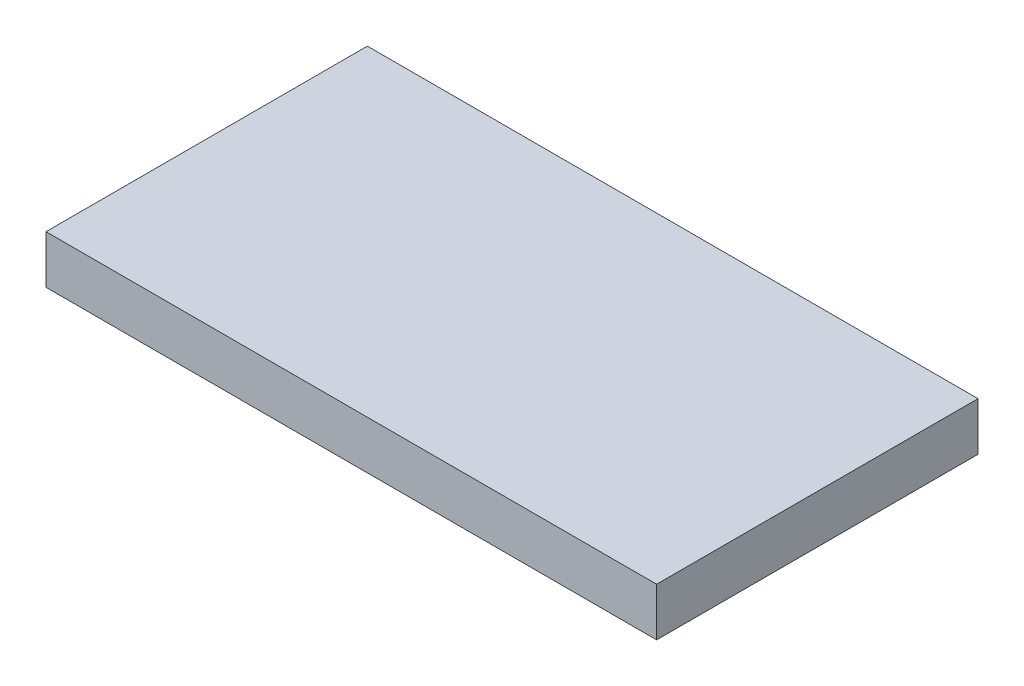
SolidWorks part; units mm, degrees
material "Acrylic (Medium-high impact)"
ref_plane "Front Plane" through (0, 0, 0) normal (0, 0, 1) x (1, 0, 0)
ref_plane "Top Plane" through (0, 0, 0) normal (0, 1, 0) x (1, 0, 0)
ref_plane "Right Plane" through (0, 0, 0) normal (1, 0, 0) x (0, 0, -1)
sketch "Sketch1" plane through (0, 0, 0) normal (0, 1, 0) x (1, 0, 0)
  line L1 (-475.0685, -251.5548) -> (490.1315, -251.5548)
  line L2 (-475.0685, -251.5548) -> (-475.0685, 256.4452)
  line L3 (-475.0685, 256.4452) -> (490.1315, 256.4452)
  line L4 (490.1315, -251.5548) -> (490.1315, 256.4452)
  circle A0 centre (-246.4685, 154.8452) radius 1000
  circle A8 centre (-246.4685, 154.8452) radius 25.4
  circle A10 centre (261.5315, 154.8452) radius 25.4
  circle A11 centre (261.5315, -149.9548) radius 25.4
  circle A12 centre (-246.4685, -149.9548) radius 25.4
  point P1 (0, 0)
  dimension "D3" = 101.6
  dimension "D4" = 50.8
  dimension "D1" = 508
  dimension "D2" = 965.2
  dimension "D5" = 228.6
extrude "Boss-Extrude1" add sketch "Sketch1" along normal blind 76.2 contours L1 L4 L3 L2
extrude "Cut-Extrude1" cut sketch "Sketch1<5>" along normal blind 25.4 contours A12 | A11 | A10 | A8
sketch "Sketch1<5>" plane through (0, 0, 0) normal (0, 1, 0) x (1, 0, 0) same geometry as "Sketch1"
